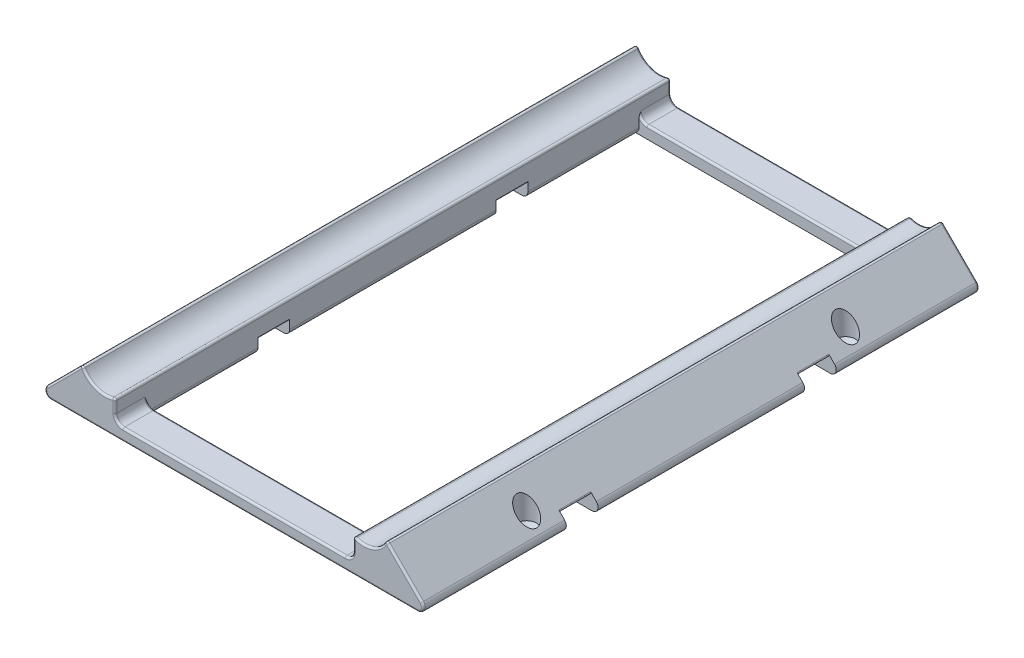
SolidWorks part; units mm, degrees
material "ABS"
ref_plane "Front Plane" through (0, 0, 0) normal (0, 0, 1) x (1, 0, 0)
ref_plane "Top Plane" through (0, 0, 0) normal (0, 1, 0) x (1, 0, 0)
ref_plane "Right Plane" through (0, 0, 0) normal (1, 0, 0) x (0, 0, -1)
sketch "Sketch1" plane through (0, 0, 0) normal (0, 0, 1) x (1, 0, 0)
  line L0 (-58.0879, 0) -> (-46.562, 11.5258)
  line L1 (-58.0879, 0) -> (-38.2879, 0)
  line L3 (-38.2879, 0) -> (-38.2879, 8.5)
  line L4 (-38.2879, 0) -> (21.7121, 0)
  line L5 (-8.2879, 0) -> (-8.2879, -25.3276) construction
  line L7 (21.7121, 3) -> (-38.2879, 3)
  line L8 (21.7121, 0) -> (21.7121, 8.5)
  line L9 (41.5121, 0) -> (21.7121, 0)
  line L10 (41.5121, 0) -> (29.9863, 11.5258)
  arc A1 (-46.562, 11.5258) -> (-38.2879, 8.5) centre (-40.912, 14.15) ccw
  arc A2 (29.9863, 11.5258) -> (21.7121, 8.5) centre (24.3363, 14.15) cw
  dimension "D4" = 8.5
  dimension "D5" = 30
  dimension "D1" = 16.3
  dimension "D2" = 19.8
  dimension "D3" = 45
extrude "Boss-Extrude1" add sketch "Sketch1" against normal blind 140 contours L10 A2 L8 L9 | L4 L8 L7 L3 | A1 L0 L1 L3 region at (-46.3645, 4.124, 0) region at (-8.2879, 1.5, 0) region at (29.7888, 4.124, 0)
sketch "Sketch2" plane through (0, 3, 0) normal (0, 1, 0) x (1, 0, 0)
  line L6 (21.7121, 132) -> (-38.2879, 132)
  line L7 (21.7121, 132) -> (-38.2879, 132)
  line L8 (-38.2879, 140) -> (-38.2879, 0) construction
  line L9 (21.7121, 8) -> (-38.2879, 8)
  line L10 (21.7121, 8) -> (-38.2879, 8)
  line L11 (-38.2879, 132) -> (-38.2879, 8)
  line L12 (21.7121, 140) -> (21.7121, 0) construction
  line L13 (21.7121, 132) -> (21.7121, 8)
  dimension "D1" = 8
  dimension "D2" = 8
extrude "Cut-Extrude1" cut sketch "Sketch2" against normal through all
sketch "Sketch3" plane through (21.7121, 0, 0) normal (-1, 0, 0) x (0, 0, 1)
  line L0 (-70, 11.5258) -> (-70, -6.476) construction
  line L3 (-96, 0) -> (-104, 0)
  line L4 (-140, 11.5258) -> (0, 11.5258) construction
  line L5 (-8, 0) -> (-132, 0) construction
  line L10 (-44, 0) -> (-36, 0)
  line L11 (-44, 0) -> (-44, 3.5)
  line L12 (-44, 3.5) -> (-36, 3.5)
  line L13 (-36, 0) -> (-36, 3.5)
  line L14 (-104, 0) -> (-104, 3.5)
  line L15 (-96, 3.5) -> (-104, 3.5)
  line L16 (-96, 0) -> (-96, 3.5)
  point P9 (-70, 5.75)
  dimension "D1" = 3.5
  dimension "D2" = 8
extrude "Cut-Extrude2" cut sketch "Sketch3" against normal through all both and the other way through all
ref_plane "Plane1" through (0, 2, 0) normal (0, -1, 0) x (-1, 0, 0)
sketch "Sketch5" plane through (0, 2, 0) normal (0, -1, 0) x (-1, 0, 0)
  line L5 (58.0879, 70) -> (-41.5121, 70) construction
  line L6 (58.0879, 96) -> (58.0879, 44) construction
  line L7 (-41.5121, 96) -> (-41.5121, 44) construction
  line L9 (8.2879, 0) -> (8.2879, 140) construction
  line L10 (-21.7121, 0) -> (38.2879, 0) construction
  line L11 (-21.7121, 140) -> (38.2879, 140) construction
  circle A0 centre (52.1379, 110.15) radius 2.5
  circle A1 centre (52.1379, 29.85) radius 2.5
  circle A2 centre (-35.5621, 29.85) radius 2.5
  circle A3 centre (-35.5621, 110.15) radius 2.5
  point P35 (52.1379, 29.85)
  point P40 (-35.5621, 29.85)
  point P42 (-35.5621, 110.15)
  point P43 (52.1379, 110.15)
  dimension "D1" = 5
  dimension "D2" = 5
  dimension "D3" = 5
  dimension "D4" = 5
hole_wizard "CSK for M2 Flat Head Machine Screw2" positions "Sketch5" profile "Sketch7" countersink size "M2" standard "ANSI Metric" end condition through all
sketch "Sketch7" plane through (-52.1379, 2, -110.15) normal (1, 0, 0) x (0, 0, 1)
  line L0 (0, 0) -> (0, 2)
  line L1 (0, 2) -> (0.75, 2)
  line L2 (0.75, 2) -> (0.75, 1.75)
  line L3 (0.75, 1.75) -> (2.5, 0)
  line L5 (2.5, 0) -> (0, 0)
  line L6 (-0.75, 1.75) -> (-2.5, 0) construction
  line L11 (0, -6.35) -> (0, 107.95) construction
  dimension "Thru Hole Dia." = 1.5
  dimension "Thru Hole Depth" = 2
  dimension "Near C'Sink Dia." = 5
  dimension "Near C'Sink Angle" = 90
extrude "Cut-Extrude3" cut sketch "Sketch5" against normal through all
fillet "Fillet1" radius 2 4 edges at (21.7121, 3, -4) (-38.2879, 3, -4) (-38.2879, 3, -136) (21.7121, 3, -136)
fillet "Fillet2" radius 0.3 8 edges at (-38.2879, 3.5, -100) (21.7121, 3.5, -100) (21.7121, 3.5, -40) (38.0121, 3.5, -40) (-38.2879, 3.5, -40) (38.0121, 3.5, -100) (-54.5879, 3.5, -40) (-54.5879, 3.5, -100)
fillet "Fillet3" radius 0.5 30 edges at (-37.7021, 3.5858, -8) (21.1264, 3.5858, -8) (21.1264, 3.5858, -132) (-37.7021, 3.5858, -132) (21.7121, 6.75, -140) (21.1264, 3.5858, -140) (-37.7021, 3.5858, -140) (-38.2879, 6.75, -140) (-52.3249, 5.7629, -140) (-8.2879, 0, -140) (35.7492, 5.7629, -140) (-8.2879, 3, -8) (-8.2879, 3, -132) (-8.2879, 3, -140) (-46.562, 11.5258, -70) (-43.0516, 8.2993, -140) (-38.2879, 8.5, -70) (21.7121, 8.5, -70) (26.4759, 8.2993, -140) (29.9863, 11.5258, -70) (-8.2879, 0, 0) (-52.3249, 5.7629, 0) (-43.0516, 8.2993, 0) (-38.2879, 6.75, 0) (-37.7021, 3.5858, 0) (-8.2879, 3, 0) (21.1264, 3.5858, 0) (21.7121, 6.75, 0) (26.4759, 8.2993, 0) (35.7492, 5.7629, 0)
fillet "Fillet4" radius 1.5 6 edges at (-38.2879, 0, -118) (-38.2879, 0, -22) (-38.2879, 0, -70) (21.7121, 0, -22) (21.7121, 0, -118) (21.7121, 0, -70)
fillet "Fillet5" radius 1.5 10 edges at (41.1586, 0.1464, -0.1464) (41.1586, 0.1464, -139.8536) (-57.7343, 0.1464, -139.8536) (-57.7343, 0.1464, -0.1464) (-58.0879, 0, -18.25) (-58.0879, 0, -70) (-58.0879, 0, -121.75) (41.5121, 0, -121.75) (41.5121, 0, -70) (41.5121, 0, -18.25)
